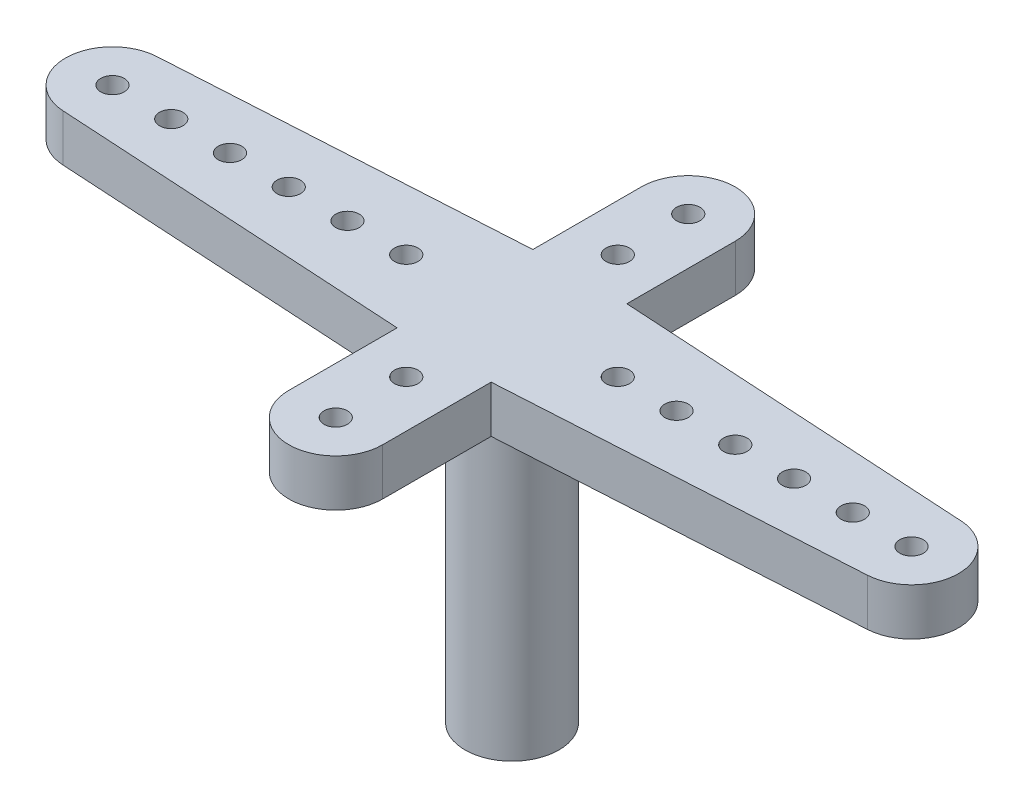
SolidWorks part; units mm, degrees
material "ABS"
ref_plane "Front Plane" through (0, 0, 0) normal (0, 0, 1) x (1, 0, 0)
ref_plane "Top Plane" through (0, 0, 0) normal (0, 1, 0) x (1, 0, 0)
ref_plane "Right Plane" through (0, 0, 0) normal (1, 0, 0) x (0, 0, -1)
sketch "Sketch1" plane through (0, 0, 0) normal (0, 1, 0) x (1, 0, 0)
  line L0 (-36.3167, 0) -> (36.3167, 0) construction
  line L1 (0, 19.7064) -> (0, -19.7064) construction
  line L2 (2, 7.5) -> (2, 2.8874)
  line L3 (17.1176, 1.9965) -> (2, 2.8874)
  line L4 (17.1176, -1.9965) -> (2, -2.8874)
  line L5 (-17.1176, -1.9965) -> (-2, -2.8874)
  line L6 (-17.1176, 1.9965) -> (-2, 2.8874)
  line L7 (-2, 7.5) -> (-2, 2.8874)
  line L8 (2, -7.5) -> (2, -2.8874)
  line L9 (-2, -7.5) -> (-2, -2.8874)
  line L10 (-2, 2.8874) -> (-0.1765, 2.9948) construction
  line L11 (2, 2.8874) -> (0.1765, 2.9948) construction
  line L12 (2, -2.8874) -> (0.1765, -2.9948) construction
  line L13 (-2, -2.8874) -> (-0.1765, -2.9948) construction
  circle A0 centre (0, 0) radius 2
  arc A1 (17.1176, 1.9965) -> (17.1176, -1.9965) centre (17, 0) cw
  arc A2 (-2, 7.5) -> (2, 7.5) centre (0, 7.5) cw
  circle A3 centre (0, 0) radius 3 construction
  arc A4 (-17.1176, 1.9965) -> (-17.1176, -1.9965) centre (-17, 0) ccw
  arc A5 (-2, -7.5) -> (2, -7.5) centre (0, -7.5) ccw
  circle A7 centre (-17, 0) radius 0.5
  circle A8 centre (17, 0) radius 0.5
  circle A9 centre (-14.5, 0) radius 0.5
  circle A10 centre (-12, 0) radius 0.5
  circle A11 centre (-9.5, 0) radius 0.5
  circle A12 centre (-7, 0) radius 0.5
  circle A13 centre (-4.5, 0) radius 0.5
  circle A14 centre (4.5, 0) radius 0.5
  circle A15 centre (7, 0) radius 0.5
  circle A16 centre (9.5, 0) radius 0.5
  circle A17 centre (12, 0) radius 0.5
  circle A18 centre (14.5, 0) radius 0.5
  circle A19 centre (0, 7.5) radius 0.5
  circle A20 centre (0, 4.5) radius 0.5
  circle A21 centre (0, -4.5) radius 0.5
  circle A22 centre (0, -7.5) radius 0.5
  point P6 (0, 0)
  point P9 (0, 0)
  dimension "D1" = 4
  dimension "D3" = 2
  dimension "D5" = 2
  dimension "D6" = 6
  dimension "D7" = 1
  dimension "D9" = 4.5
  dimension "D10" = 1
  dimension "D2" = 17
  dimension "D4" = 7.5
  dimension "D12" = 4.5
  dimension "D8" = 6
  dimension "D11" = 2
extrude "Boss-Extrude1" add sketch "Sketch1" along normal blind 2
extrude "Boss-Extrude2" add sketch "Sketch1<3>" against normal blind 15 from surface contours A0 region at (0, 0, 0) starting at face at (0, 2, 0)
sketch "Sketch1<3>" plane through (0, 0, 0) normal (0, 1, 0) x (1, 0, 0) same geometry as "Sketch1"
